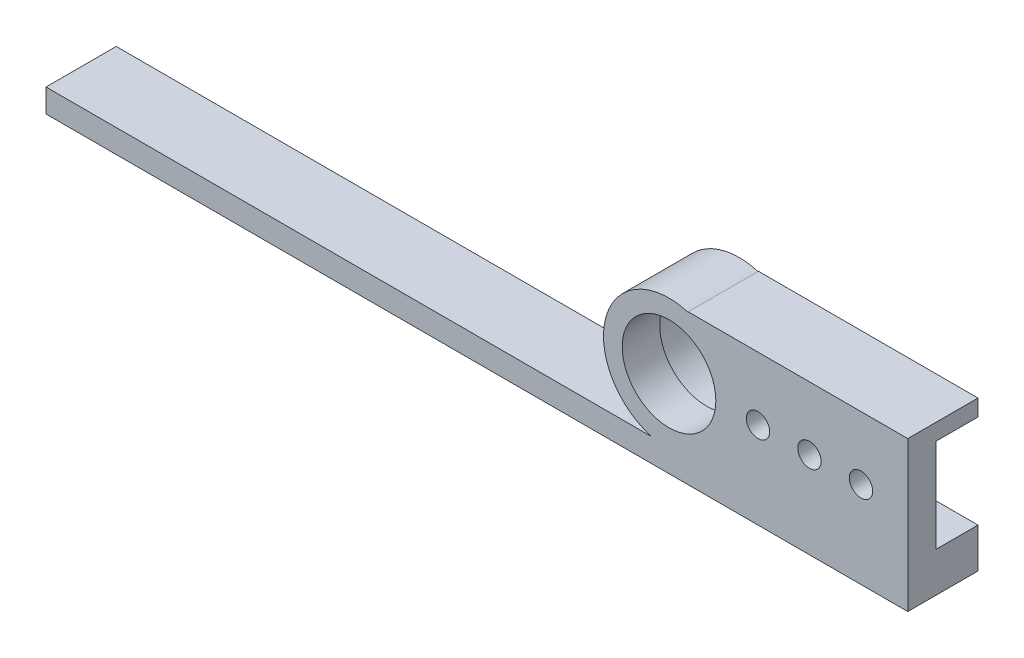
SolidWorks part; units mm, degrees
ref_plane "前视基准面" through (0, 0, 0) normal (0, 0, 1) x (1, 0, 0)
ref_plane "上视基准面" through (0, 0, 0) normal (0, 1, 0) x (1, 0, 0)
ref_plane "右视基准面" through (0, 0, 0) normal (1, 0, 0) x (0, 0, -1)
sketch "草图1" plane through (0, 0, 0) normal (0, 0, 1) x (1, 0, 0)
  line L1 (20, -10) -> (-20, -10)
  line L2 (20, -10) -> (20, 10)
  line L3 (20, 10) -> (-20, 10)
  line L4 (-20, -10) -> (-20, 10)
  line L5 (20, -10) -> (-20, 10) construction
  line L6 (20, 10) -> (-20, -10) construction
  point P0 (0, 0)
  dimension "D1" = 40
  dimension "D2" = 20
extrude "凸台-拉伸1" add sketch "草图1" along normal blind 6
sketch "草图2" plane through (0, 0, 6) normal (0, 0, 1) x (1, 0, 0)
  line L0 (20, -10) -> (20, 10) construction
  circle A0 centre (10, 0) radius 2.5
  circle A1 centre (-1, 0) radius 2.5
  circle A2 centre (-12, 0) radius 2.5
  dimension "D1" = 10
  dimension "D2" = 5
  dimension "D3" = 3
extrude "切除-拉伸1" cut sketch "草图2" against normal through all
sketch "草图3" plane through (0, 0, 6) normal (0, 0, 1) x (1, 0, 0)
  line L0 (20, 13.5) -> (20, 10)
  line L1 (20, -13.5) -> (-26.894, -13.5)
  line L3 (20, 13.5) -> (-26.894, 13.5)
  line L4 (-20, 10) -> (-20, -10)
  line L5 (-20, -10) -> (20, -10)
  line L6 (20, -10) -> (20, 10)
  line L7 (20, 10) -> (-20, 10)
  line L8 (-20, 10) -> (-20, -10)
  line L9 (-20, -10) -> (20, -10)
  line L10 (20, -10) -> (20, 10)
  line L11 (20, 10) -> (-20, 10)
  line L12 (-26.894, -13.5) -> (-26.894, 13.5)
  line L13 (20, -10.0394) -> (-26.894, 13.5) construction
  line L14 (20, 10.0394) -> (-26.894, -13.5) construction
  line L15 (20, -10) -> (20, -13.5)
  circle A0 centre (-31, 0) radius 11
  circle A1 centre (-31, 0) radius 14
  point P2 (0, 0)
  line M10 (-20, 10) -> (-20, -10)
  line M11 (-20, -10) -> (20, -10)
  line M13 (20, 10) -> (-20, 10)
  dimension "D3" = 22
  dimension "D4" = 28
  dimension "D2" = 3.5
  dimension "D1" = 0
extrude "凸台-拉伸2" add sketch "草图3" against normal blind 15 contours L3 A1 L1 L12 A0 | A1 L1 L15 M11 M10 | L1 A1 L8 A0 L12 | L8 A1 L3 L12 A0 | L8 A1 | A1 L0 L3 M10 M13 region at (-1.9449, 11.7771, 6) region at (-1.9449, -11.7771, 6) region at (-23.0173, 9.0328, 6) region at (-27.2274, 11.7946, 6) region at (-18.7882, 0, 6) region at (-23.0173, -9.0328, 6)
sketch "草图5" plane through (0, 0, 6) normal (0, 0, 1) x (1, 0, 0)
  circle A0 centre (-31, 0) radius 10
  circle A1 centre (-31, 0) radius 11 construction
  circle A2 centre (-31, 0) radius 11
  dimension "D1" = 20
extrude "凸台-拉伸3" add sketch "草图5" against normal blind 8
sketch "草图6" plane through (0, 0, 6) normal (0, 0, 1) x (1, 0, 0)
  circle A0 centre (-31, 0) radius 8.5
  circle A1 centre (-31, 0) radius 10 construction
  circle A2 centre (-31, 0) radius 10
  dimension "D1" = 17
sketch "草图9" plane through (0, -13.5, 0) normal (0, -1, 0) x (1, 0, 0)
  circle A0 centre (-18.2368, -1.344) radius 5.5352
sketch "草图10" plane through (20, 0, 0) normal (1, 0, 0) x (0, 0, -1)
  line L1 (9, -13.5) -> (-6, -13.5)
  line L2 (9, -13.5) -> (9, -18.5)
  line L3 (9, -18.5) -> (-6, -18.5)
  line L4 (-6, -13.5) -> (-6, -18.5)
  dimension "D1" = 5
extrude "凸台-拉伸4" add sketch "草图10" against normal blind 200
sketch "草图11" plane through (0, 0, 6) normal (0, 0, 1) x (1, 0, 0)
  line L1 (-28.6193, -11.8661) -> (-25.5243, -11.8661)
  line L2 (-28.6193, -11.8661) -> (-28.6193, -14.961)
  line L3 (-28.6193, -14.961) -> (-25.5243, -14.961)
  line L4 (-25.5243, -11.8661) -> (-25.5243, -14.961)
extrude "凸台-拉伸5" add sketch "草图11" against normal through all
sketch "草图13" plane through (0, -18.5, 0) normal (0, -1, 0) x (1, 0, 0)
  line L0 (-164.0842, 6) -> (-164.0842, -9)
  line L1 (-180, 6) -> (20, 6) construction
  line L2 (-164.0842, 128.4982) -> (-164.0842, -241.5018) construction
  line L3 (-180, -9) -> (20, -9) construction
sketch "草图14" plane through (0, -18.5, 0) normal (0, -1, 0) x (1, 0, 0)
  line L0 (-118.4338, -15.7251) -> (-118.4338, 9.3691)
  line L1 (-118.4338, 126.7017) -> (-118.4338, -243.2983) construction
sketch "草图15" plane through (0, -18.5, 0) normal (0, -1, 0) x (1, 0, 0)
  line L1 (-118.4338, -15.7251) -> (-184.1416, -15.7251)
  line L2 (-118.4338, -15.7251) -> (-118.4338, 11.9644)
  line L3 (-118.4338, 11.9644) -> (-184.1416, 11.9644)
  line L4 (-184.1416, -15.7251) -> (-184.1416, 11.9644)
sketch "草图16" plane through (0, -18.5, 0) normal (0, -1, 0) x (1, 0, 0)
  line L0 (-164.0842, 6.4407) -> (-164.0842, -38.9947)
  line L1 (-164.0842, 128.4982) -> (-164.0842, -241.5018) construction
sketch "草图17" plane through (0, -18.5, 0) normal (0, -1, 0) x (1, 0, 0)
  line L0 (-164.0842, 7.3332) -> (-164.0842, -35.3686)
  line L1 (-164.0842, 128.4982) -> (-164.0842, -241.5018) construction
sketch "草图18" plane through (0, -18.5, 0) normal (0, -1, 0) x (1, 0, 0)
  line L1 (-164.0842, -38.9947) -> (-206.846, -38.9947)
  line L2 (-164.0842, -38.9947) -> (-164.0842, 25.1925)
  line L3 (-164.0842, 25.1925) -> (-206.846, 25.1925)
  line L4 (-206.846, -38.9947) -> (-206.846, 25.1925)
extrude "切除-拉伸3" cut sketch "草图18" against normal through all
